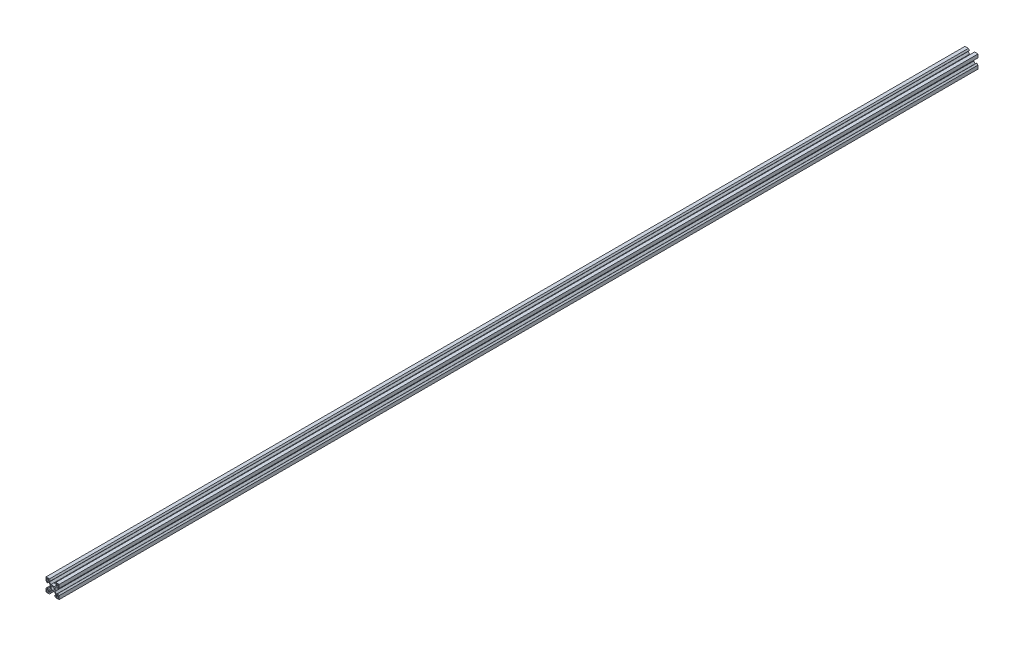
SolidWorks part; units mm, degrees
ref_plane "Спереди" through (0, 0, 0) normal (0, 0, 1) x (1, 0, 0)
ref_plane "Сверху" through (0, 0, 0) normal (0, 1, 0) x (1, 0, 0)
ref_plane "Справа" through (0, 0, 0) normal (1, 0, 0) x (0, 0, -1)
sketch "Эскиз1" plane through (0, 0, 0) normal (0, 0, 1) x (1, 0, 0)
  line L0 (-7.5, 7.5) -> (7.5, 7.5) construction
  line L1 (-10, -10) -> (10, -10) construction
  line L2 (-10, -10) -> (-10, 10) construction
  line L3 (-10, 10) -> (-4.75, 10)
  line L4 (10, -10) -> (10, 10) construction
  line L5 (-10, -10) -> (10, 10) construction
  line L6 (-10, 10) -> (10, -10) construction
  line L7 (7.5, 7.5) -> (7.5, -7.5) construction
  line L8 (7.5, -7.5) -> (-7.5, -7.5) construction
  line L9 (-7.5, -7.5) -> (-7.5, 7.5) construction
  line L10 (-7.5, 7.5) -> (7.5, -7.5) construction
  line L11 (-7.5, -7.5) -> (7.5, 7.5) construction
  line L12 (-4.75, 10) -> (-3.1, 8)
  line L13 (-3.1, 8) -> (-4.95, 8)
  line L14 (-4.95, 8) -> (-4.95, 5.85)
  line L15 (-4.95, 5.85) -> (-2.6, 3.5)
  line L16 (-2.6, 3.5) -> (2.6, 3.5)
  line L17 (2.6, 3.5) -> (4.95, 5.85)
  line L18 (4.95, 5.85) -> (4.95, 8)
  line L19 (4.95, 8) -> (3.1, 8)
  line L20 (3.1, 8) -> (4.75, 10)
  line L21 (4.75, 10) -> (10, 10)
  line L22 (-4.75, 10) -> (4.75, 10) construction
  line L23 (-3.1, 8) -> (3.1, 8) construction
  line L24 (-4.95, 5.85) -> (4.95, 5.85) construction
  line L25 (-2.6, 3.5) -> (0, 0) construction
  line L26 (-9.15, 5.85) -> (-5.85, 5.85)
  line L27 (-9.15, 5.85) -> (-9.15, 9.15)
  line L28 (-9.15, 9.15) -> (-5.85, 9.15)
  line L29 (-5.85, 5.85) -> (-5.85, 9.15)
  line L30 (-9.15, 5.85) -> (-5.85, 9.15) construction
  line L31 (-9.15, 9.15) -> (-5.85, 5.85) construction
  line L32 (9.15, 5.85) -> (5.85, 5.85)
  line L33 (9.15, 5.85) -> (9.15, 9.15)
  line L34 (9.15, 9.15) -> (5.85, 9.15)
  line L35 (5.85, 5.85) -> (5.85, 9.15)
  line L36 (9.15, 5.85) -> (5.85, 9.15) construction
  line L37 (9.15, 9.15) -> (5.85, 5.85) construction
  line L38 (9.15, -9.15) -> (5.85, -9.15)
  line L39 (9.15, -9.15) -> (9.15, -5.85)
  line L40 (9.15, -5.85) -> (5.85, -5.85)
  line L41 (5.85, -9.15) -> (5.85, -5.85)
  line L42 (9.15, -9.15) -> (5.85, -5.85) construction
  line L43 (9.15, -5.85) -> (5.85, -9.15) construction
  line L44 (-9.15, -5.85) -> (-5.85, -5.85)
  line L45 (-9.15, -5.85) -> (-9.15, -9.15)
  line L46 (-9.15, -9.15) -> (-5.85, -9.15)
  line L47 (-5.85, -5.85) -> (-5.85, -9.15)
  line L48 (-9.15, -5.85) -> (-5.85, -9.15) construction
  line L49 (-9.15, -9.15) -> (-5.85, -5.85) construction
  line L50 (3.5, 2.6) -> (0, 0) construction
  line L51 (3.5, 2.6) -> (3.5, -2.6)
  line L52 (5.85, 4.95) -> (3.5, 2.6)
  line L53 (3.5, -2.6) -> (5.85, -4.95)
  line L54 (5.85, -4.95) -> (8, -4.95)
  line L55 (8, -4.95) -> (8, -3.1)
  line L56 (8, -3.1) -> (10, -4.75)
  line L57 (8, 4.95) -> (5.85, 4.95)
  line L58 (8, 3.1) -> (8, 4.95)
  line L59 (10, 4.75) -> (8, 3.1)
  line L60 (2.6, -3.5) -> (0, 0) construction
  line L61 (2.6, -3.5) -> (-2.6, -3.5)
  line L62 (4.95, -5.85) -> (2.6, -3.5)
  line L63 (-2.6, -3.5) -> (-4.95, -5.85)
  line L64 (-4.95, -5.85) -> (-4.95, -8)
  line L65 (-4.95, -8) -> (-3.1, -8)
  line L66 (-3.1, -8) -> (-4.75, -10)
  line L67 (4.95, -8) -> (4.95, -5.85)
  line L68 (3.1, -8) -> (4.95, -8)
  line L69 (4.75, -10) -> (3.1, -8)
  line L70 (-3.5, -2.6) -> (0, 0) construction
  line L71 (-3.5, -2.6) -> (-3.5, 2.6)
  line L72 (-5.85, -4.95) -> (-3.5, -2.6)
  line L73 (-3.5, 2.6) -> (-5.85, 4.95)
  line L74 (-5.85, 4.95) -> (-8, 4.95)
  line L75 (-8, 4.95) -> (-8, 3.1)
  line L76 (-8, 3.1) -> (-10, 4.75)
  line L77 (-8, -4.95) -> (-5.85, -4.95)
  line L78 (-8, -3.1) -> (-8, -4.95)
  line L79 (-10, -4.75) -> (-8, -3.1)
  line L80 (-10, 10) -> (-10, 4.75)
  line L81 (-10, -4.75) -> (-10, -10)
  line L82 (-10, -10) -> (-4.75, -10)
  line L83 (4.75, -10) -> (10, -10)
  line L84 (10, -10) -> (10, -4.75)
  line L85 (10, 4.75) -> (10, 10)
  circle A0 centre (-7.5, 7.5) radius 1.65 construction
  circle A1 centre (7.5, 7.5) radius 1.65 construction
  circle A2 centre (7.5, -7.5) radius 1.65 construction
  circle A3 centre (-7.5, -7.5) radius 1.65 construction
  circle A4 centre (0, 0) radius 2.5
  point P0 (0, 0)
  point P14 (0, 0)
  point P15 (0, 3.5)
  point P26 (0, 5.85)
  point P27 (0, 8)
  point P28 (0, 10)
  point P80 (0, 0)
  dimension "D3" = 3.3
  dimension "D4" = 3.3
  dimension "D5" = 3.3
  dimension "D6" = 3.3
  dimension "D14" = 5
  dimension "D1" = 20
  dimension "D2" = 20
  dimension "D7" = 15
  dimension "D8" = 6.2
  dimension "D9" = 9.9
  dimension "D10" = 9.5
  dimension "D11" = 2
  dimension "D12" = 6.5
  dimension "D15" = 4
extrude "Бобышка-Вытянуть1" add sketch "Эскиз1" against normal up to surface (1400 mm away)
